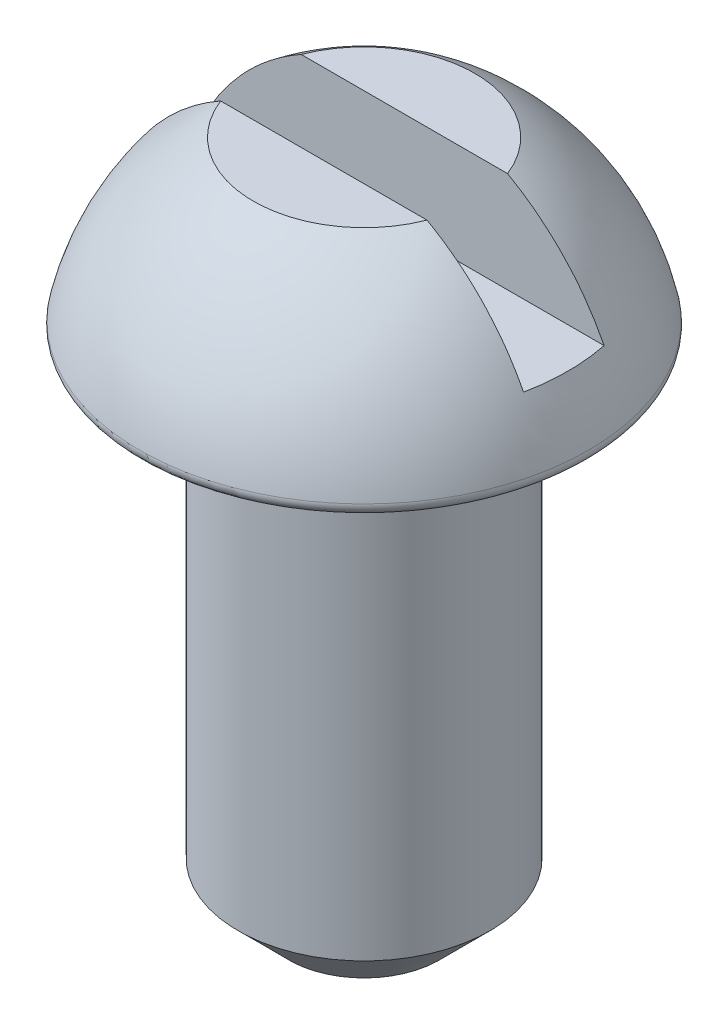
SolidWorks part; units mm, degrees
ref_plane "Спереди" through (0, 0, 0) normal (0, 0, 1) x (1, 0, 0)
ref_plane "Сверху" through (0, 0, 0) normal (0, 1, 0) x (1, 0, 0)
ref_plane "Справа" through (0, 0, 0) normal (1, 0, 0) x (0, 0, -1)
sketch "Эскиз1" plane through (0, 0, 0) normal (0, 0, 1) x (1, 0, 0)
  line L0 (2.25, 5) -> (1.25, 5)
  line L1 (0, 0) -> (0, 6.7)
  line L2 (1.25, 5) -> (1.25, 0.5)
  line L3 (1.25, 0.5) -> (0.75, 0)
  line L4 (0.75, 0) -> (0, 0)
  line L5 (0, 6.7) -> (1.1, 6.7)
  arc A0 (1.1, 6.7) -> (2.25, 5) centre (-0.1634, 4.6064) cw
  dimension "D2" = 1.1
  dimension "D8" = 2.1
  dimension "D1" = 5
  dimension "D3" = 1.25
  dimension "D4" = 0.75
  dimension "D5" = 1.7
  dimension "D6" = 2.25
  dimension "D7" = 45
revolve "Повернуть1" add sketch "Эскиз1" angle 360 about L1
fillet "Скругление1" radius 0.1 1 edges at (0, 5, -2.25)
sketch "Эскиз3" plane through (0, 6.7, 0) normal (0, 1, 0) x (-1, 0, 0)
  line L1 (2.5, -0.4) -> (-2.5, -0.4)
  line L2 (2.5, -0.4) -> (2.5, 0.4)
  line L3 (2.5, 0.4) -> (-2.5, 0.4)
  line L4 (-2.5, -0.4) -> (-2.5, 0.4)
  dimension "D1" = 0.8
  dimension "D2" = 0.4
  dimension "D3" = 5
  dimension "D4" = 2.5
extrude "Вырез-Вытянуть2" cut sketch "Эскиз3" against normal blind 1
ref_axis "Ось1" through (0, -104.1565, 0) along (0, 1, 0)
